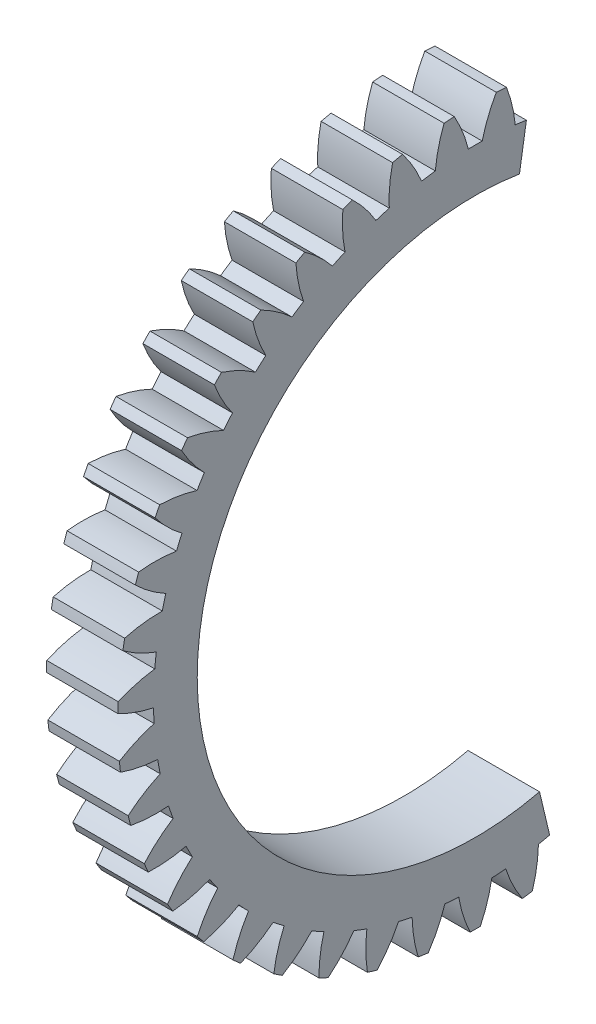
SolidWorks part; units mm, degrees
ref_plane "Plane1" through (0, 0, 0) normal (0, 0, 1) x (1, 0, 0)
ref_plane "Plane2" through (0, 0, 0) normal (0, 1, 0) x (1, 0, 0)
ref_plane "Plane3" through (0, 0, 0) normal (1, 0, 0) x (0, 0, -1)
sketch "HoldingSke" plane through (0, 0, 0) normal (0, 1, 0) x (1, 0, 0)
  line L0 (0, 0) -> (0.3657, -0.341)
  line L1 (-15, 0) -> (100, 0) construction
  line L2 (0, 0) -> (-2.1039, 2.3779)
  line L3 (0, 0) -> (-11.863, 4.5341)
  line L4 (0, 0) -> (6.316, 5.8897)
  line L5 (0, 0) -> (-46.8476, -17.4728)
  line L6 (0, 0) -> (-7.4607, -5.0337)
  line L7 (-2.1039, 2.3779) -> (8.6587, 51.2065)
  line L8 (-76.2, 54.61) -> (-71.3, 54.61)
  line L9 (-71.009, 38.7566) -> (-53.1078, 45.2721)
  line L10 (-76.2, 71.12) -> (104.1128, 71.12)
  line L11 (0, 0) -> (-9, 0)
  line L12 (-76.2, 101.6) -> (-76.133, 101.6)
  line L13 (24.9733, 27.94) -> (52.9518, 28.4284)
  line L14 (24.9733, 27.94) -> (24.9743, 27.94)
  line L15 (24.9733, 27.94) -> (100.4006, 29.5858)
  line L16 (-63.627, -2) -> (-12.827, -2)
  circle A0 centre (0, 0) radius 35
  circle A1 centre (0, 0) radius 37.5
  circle A2 centre (0, 0) radius 37.5
  circle A3 centre (0, 0) radius 35
  dimension "Num_teeth" = 43
  dimension "Pitch_radius" = 180.3128
  dimension "Width" = 9
  dimension "Thickness" = 9
sketch "BasProSke" plane through (0, 0, 0) normal (0, 1, 0) x (1, 0, 0)
  line L0 (-10, 0) -> (60, 0) construction
  line L1 (0, 0) -> (0, 45)
  line L2 (0, 0) -> (9, 0)
  line L3 (9, 0) -> (9, 45)
  line L4 (9, 45) -> (0, 45)
  dimension "Thickness" = 9
  dimension "Diameter" = 90
revolve "Base-Revolve" add sketch "BasProSke" angle 360 about L0
sketch "TooCutSke" plane through (0, 0, 0) normal (1, 0, 0) x (0, 0, -1)
  line L1 (0, 0) -> (0, 107) construction
  line L2 (0, 0) -> (-1.6877, 42.9669) construction
  line L3 (0, 0) -> (-6.274, 85.7216) construction
  line L4 (-1.6877, 42.9669) -> (-3.137, 42.8608) construction
  arc A0 (0.8751, 40.4895) -> (-0.8751, 40.4895) centre (0, 0) ccw
  arc A1 (2.6611, 44.9467) -> (-2.6611, 44.9467) centre (0, 0) ccw
  circle A2 centre (0, 0) radius 43 construction
  circle A3 centre (0, 0) radius 40.4068 construction
  arc A4 (-0.8751, 40.4895) -> (-2.6611, 44.9467) centre (-17.5777, 36.3831) ccw
  arc A5 (2.6611, 44.9467) -> (0.8751, 40.4895) centre (17.5777, 36.3831) ccw
extrude "ToothCut" cut sketch "TooCutSke" along normal through all
fillet "Breaks" [suppressed] radius 0.04 tangent propagation no
fillet "RootFillets" [suppressed] radius 0.501
pattern_circular "TeethCuts" count 43 every 8.372 about axis through (-10, 0, 0) along (1, 0, 0) of "ToothCut", "RootFillets", "Breaks"
sketch "HubNeaOneSke" plane through (0, 0, 0) normal (-1, 0, 0) x (0, 0, 1)
  circle A0 centre (0, 0) radius 37.5
  dimension "Diameter" = 75
extrude "HubNearOne" [suppressed] add sketch "HubNeaOneSke" along normal blind 41.0007
sketch "HubNeaBotSke" plane through (0, 0, 0) normal (-1, 0, 0) x (0, 0, 1)
  circle A0 centre (0, 0) radius 37.5
  dimension "Diameter" = 75
extrude "HubNearBoth" [suppressed] add sketch "HubNeaBotSke" along normal blind 20.5003
ref_plane "FarPln" through (9, 0, 0) normal (1, 0, 0) x (0, 0, -1)
sketch "HubFarSke" plane through (9, 0, 0) normal (1, 0, 0) x (0, 0, -1)
  circle A0 centre (0, 0) radius 37.5
  dimension "Diameter" = 75
extrude "HubFar" [suppressed] add sketch "HubFarSke" along normal blind 20.5003
sketch "BorSke" plane through (0, 0, 0) normal (1, 0, 0) x (0, 0, -1)
  circle A0 centre (0, 0) radius 35
  dimension "Diameter" = 70
extrude "Bore" cut sketch "BorSke" along normal mid plane 100.0013
sketch "KeySke" plane through (0, 0, 0) normal (1, 0, 0) x (0, 0, -1)
  line L0 (-10, 0) -> (-10, 39.9)
  line L1 (-10, 39.9) -> (10, 39.9)
  line L2 (10, 39.9) -> (10, 0)
  line L3 (0, 0) -> (0, 34) construction
  line L4 (-10, 0) -> (10, 0)
  dimension "Width" = 20
extrude "Keyway" [suppressed] cut sketch "KeySke" along normal mid plane 100.0013
pattern_circular "Keyway2" [suppressed] count 2 every 90 about axis through (-10, 0, 0) along (1, 0, 0) reverse direction yes
sketch "Szkic2" plane through (0, 0, 0) normal (1, 0, 0) x (0, 0, -1)
  line L0 (0, 0) -> (10.92, -45.9662)
  line L1 (8.0896, -34.0523) -> (9.8734, -41.5608) construction
  line L2 (10.92, -45.9662) -> (68.2286, -47.9799)
  line L3 (68.2286, -47.9799) -> (54.0532, 56.0743)
  line L4 (54.0532, 56.0743) -> (14.5542, 57.4622)
  line L5 (0, 0) -> (7.4704, 46.3991)
  line L6 (6.9571, 43.2109) -> (5.5634, 34.555) construction
  line L7 (7.4704, 46.3991) -> (14.5542, 57.4622)
  line L8 (0, 0) -> (4.6414, 28.8278)
  line L9 (4.6414, 28.8278) -> (6.2494, -26.3062)
  line L10 (0, 0) -> (6.2494, -26.3062)
  line L11 (0, 0) -> (4.6414, 28.8278) construction
  line L12 (0, 0) -> (6.2494, -26.3062) construction
  point P0 (68.2286, -47.9799)
  dimension "D1" = 120.619
  dimension "D2" = 99.77
  dimension "D3" = 105.0154
  dimension "D4" = 105.376
  dimension "D5" = 156.515
  dimension "D6" = 169.183
  dimension "D7" = 55.134
  dimension "D8" = 39.5234
  dimension "D9" = 57.344
  dimension "D10" = 13.1367
  dimension "D11" = 46.9966
extrude "Wytnij-wyciągnięcie2" cut sketch "Szkic2" along normal through all contours L5 L9 L0 L2 L3 L4 L7 region at (0, 2.7023, -34.0561)
equation "' \"Module@HoldingSke\" = 6.35"
equation "' \"Num_teeth@HoldingSke\" = 12"
equation "' \"Ap@HoldingSke\" =  20"
equation "' \"Ap@HoldingSke\" = 20"
equation "' \"Width@HoldingSke\" = 0.5 * 25.4"
equation "' \"Hub_dia@HoldingSke\"= 1 * 25.4"
equation "' \"Hub_dia@HoldingSke\" = 1 * 25.4"
equation "' \"Overall_len@HoldingSke\" = 1.0 * 25.4"
equation "' \"Bore@HoldingSke\" = 0.75 * 25.4"
equation "' \"T_dim@HoldingSke\" = 0.1 * 25.4"
equation "' \"Width@KeySke\" = 0.25 * 25.4"
equation "' \"Show_teeth@HoldingSke\" = 13"
equation "' \"Backlash@HoldingSke\" = 0.009 * 25.4"
equation "' \"Addendum_fac@HoldingSke\" = 1.0"
equation "' \"Dedendum_fac@HoldingSke\" = 1.25"
equation "' \"Dedendum_add@HoldingSke\" = 0.00005 * 25.4"
equation "' \"Clearance_fac@HoldingSke\" = 0.25"
equation "\"Pitch@HoldingSke\" = 1 / \"Module@HoldingSke\""
equation "\"Overcut_dia@TooCutSke\" = (\"Num_teeth@HoldingSke\" + 2 * \"Addendum_fac@HoldingSke\") / \"Pitch@HoldingSke\" + 0.002 * 25.4"
equation "\"Pitch_dia@TooCutSke\" = \"Num_teeth@HoldingSke\" / \"Pitch@HoldingSke\""
equation "\"Base_dia@TooCutSke\" = \"Num_teeth@HoldingSke\" / \"Pitch@HoldingSke\" * cos((\"Ap@HoldingSke\"  * 3.14159265 / 180))"
equation "\"Root_dia@TooCutSke\" = (\"Num_teeth@HoldingSke\" + 2) / \"Pitch@HoldingSke\" - 2 * (\"Addendum_fac@HoldingSke\" + \"Dedendum_fac@HoldingSke\") / \"Pitch@HoldingSke\" - \"Dedendum_add@HoldingSke\" * 2"
equation "\"Half_ang@TooCutSke\" = 180 / \"Num_teeth@HoldingSke\""
equation "\"Half_CT@TooCutSke\" = \"Num_teeth@HoldingSke\" / \"Pitch@HoldingSke\" * sin((3.14159265 / 2 / \"Num_teeth@HoldingSke\")) / 2 - 7 * \"Backlash@HoldingSke\" / 4"
equation "\"Flank_rad@TooCutSke\" = \"Num_teeth@HoldingSke\" / \"Pitch@HoldingSke\" / 5"
equation "\"Radius@RootFillets\" = \"Clearance_fac@HoldingSke\" / \"Pitch@HoldingSke\" + \"Dedendum_add@HoldingSke\""
equation "\"Break_rad@Breaks\" = 0.02 / \"Pitch@HoldingSke\""
equation "\"Thickness@HoldingSke\" = \"Width@HoldingSke\""
equation "\"OAL@HoldingSke\" = \"Thickness@HoldingSke\""
equation "\"MHD@HoldingSke\" = (\"Num_teeth@HoldingSke\" + 2) / \"Pitch@HoldingSke\" - 2 * (\"Addendum_fac@HoldingSke\" + \"Dedendum_fac@HoldingSke\")  / \"Pitch@HoldingSke\" - \"Dedendum_add@HoldingSke\" * 2"
equation "\"MBD@HoldingSke\" = (\"Num_teeth@HoldingSke\" + 2) / \"Pitch@HoldingSke\" - 2 * (\"Addendum_fac@HoldingSke\" + \"Dedendum_fac@HoldingSke\")  / \"Pitch@HoldingSke\" - \"Dedendum_add@HoldingSke\" * 2 - 0.002 * 25.4"
equation "\"MHD@HoldingSke\" = ((sgn( \"MHD@HoldingSke\" - \"Hub_dia@HoldingSke\" )-1)*( \"MHD@HoldingSke\" - \"Hub_dia@HoldingSke\" ))/-2+ \"Hub_dia@HoldingSke\""
equation "\"MBD@HoldingSke\" = ((sgn( \"MBD@HoldingSke\" - \"Bore@HoldingSke\" )-1)*( \"MBD@HoldingSke\" - \"Bore@HoldingSke\" ))/-2+ \"Bore@HoldingSke\""
equation "\"OAL@HoldingSke\" = ((sgn( \"OAL@HoldingSke\" - \"Overall_len@HoldingSke\" )+1)*( \"OAL@HoldingSke\" - \"Overall_len@HoldingSke\" ))/2 + \"Overall_len@HoldingSke\" + 0.000002 * 25.4"
equation "\"Num_teeth@TeethCuts\" = int( \"Show_teeth@HoldingSke\" ) + 1"
equation "\"Num_teeth@TeethCuts\" = ((sgn( \"Num_teeth@TeethCuts\" - \"Num_teeth@HoldingSke\" )-1)*( \"Num_teeth@TeethCuts\" - \"Num_teeth@HoldingSke\" ))/-2+ \"Num_teeth@HoldingSke\""
equation "\"Num_teeth@TeethCuts\" = ((sgn( \"Num_teeth@TeethCuts\" - 2.0)+1)*( \"Num_teeth@TeethCuts\" - 2.0))/2 +2.0"
equation "\"Angle@TeethCuts\" = 360.0 / \"Num_teeth@HoldingSke\""
equation "\"Diameter@BasProSke\" = (\"Num_teeth@HoldingSke\" + 2 * \"Addendum_fac@HoldingSke\") / \"Pitch@HoldingSke\""
equation "\"Thickness@BasProSke\"  = \"Thickness@HoldingSke\""
equation "' \"Fillet_rad@BasProSke\" =  \"Thickness@HoldingSke\" * 0.05"
equation "' \"Fillet_rad@BasProSke\" = \"Thickness@HoldingSke\" * 0.05"
equation "\"MHD@HoldingSke\" = ((sgn( \"MHD@HoldingSke\" - \"Root_dia@TooCutSke\" )-1)*( \"MHD@HoldingSke\" - \"Root_dia@TooCutSke\" ))/-2+ \"Root_dia@TooCutSke\""
equation "\"Diameter@HubNeaOneSke\" = \"MHD@HoldingSke\""
equation "\"Length@HubNearOne\" = \"OAL@HoldingSke\" - \"Thickness@BasProSke\""
equation "\"Diameter@HubNeaBotSke\" = \"MHD@HoldingSke\""
equation "\"Length@HubNearBoth\" = ( \"OAL@HoldingSke\" - \"Thickness@BasProSke\" ) / 2.0"
equation "\"Thickness@FarPln\" = \"Thickness@BasProSke\""
equation "\"Diameter@HubFarSke\" = \"MHD@HoldingSke\""
equation "\"Length@HubFar\" = ( \"OAL@HoldingSke\" - \"Thickness@BasProSke\" ) / 2.0"
equation "\"Diameter@BorSke\" = \"MBD@HoldingSke\""
equation "\"D1@Bore\" = \"OAL@HoldingSke\" * 2.0"
equation "\"D1@Keyway\" = \"OAL@HoldingSke\" * 2.0"
equation "\"Offset@KeySke\" = \"T_dim@HoldingSke\" + \"MBD@HoldingSke\" / 2.0"
